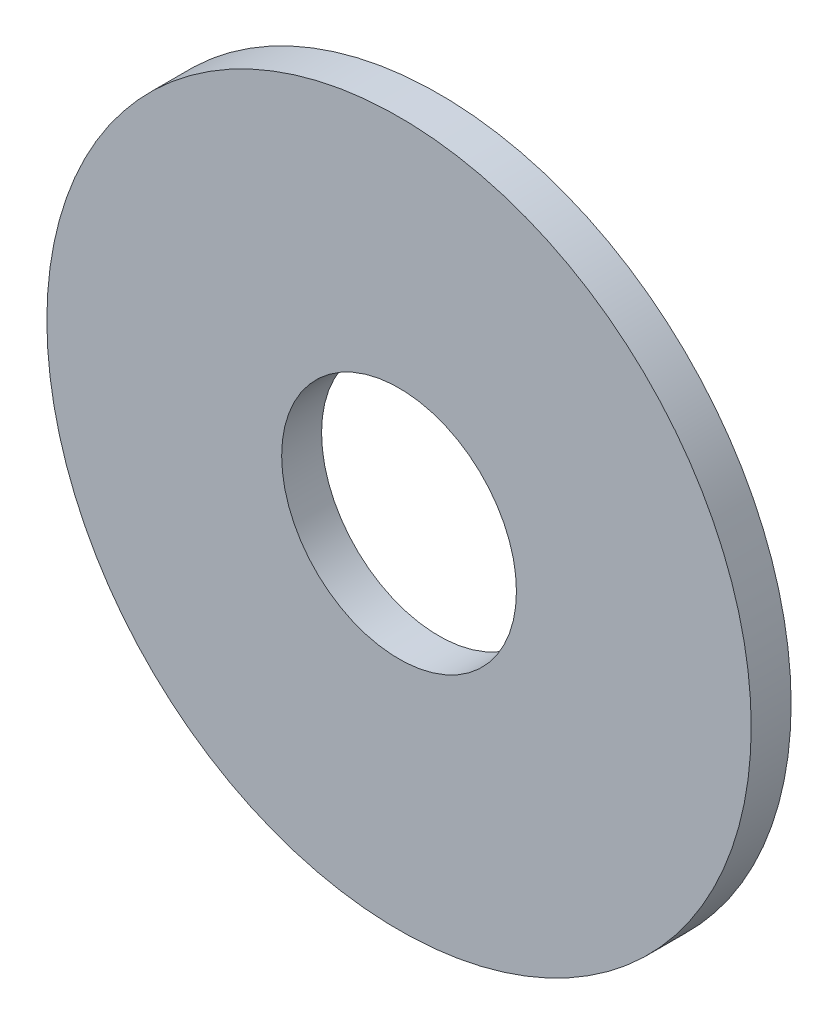
SolidWorks part; units mm, degrees
material "ABS PC"
ref_plane "Front Plane" through (0, 0, 0) normal (0, 0, 1) x (1, 0, 0)
ref_plane "Top Plane" through (0, 0, 0) normal (0, 1, 0) x (1, 0, 0)
ref_plane "Right Plane" through (0, 0, 0) normal (1, 0, 0) x (0, 0, -1)
sketch "Sketch1" plane through (0, 0, 0) normal (0, 0, 1) x (1, 0, 0)
  circle A0 centre (0, 0) radius 15
  circle A1 centre (0, 0) radius 5
  dimension "D1" = 30
  dimension "D2" = 10
extrude "Boss-Extrude1" add sketch "Sketch1" along normal blind 1.7
equation "\"smallPulleyTeeth\"= 15"
equation "\"largePulleyTeeth\"= 30"
equation "\"eighthThick\"= 2.9mm"
equation "\"sixteenthThick\" = 1.7mm"
equation "\"wheelEighthThick\"=3.0mm"
equation "\"quarterThick\"=5.6mm"
equation "\"bushingDiam\"= 7.85mm"
equation "\"plateBoltCircle\"= 65mm"
equation "\"plateBoltDiam\"= 5mm"
equation "\"D1@Boss-Extrude1\"=\"sixteenthThick\""
